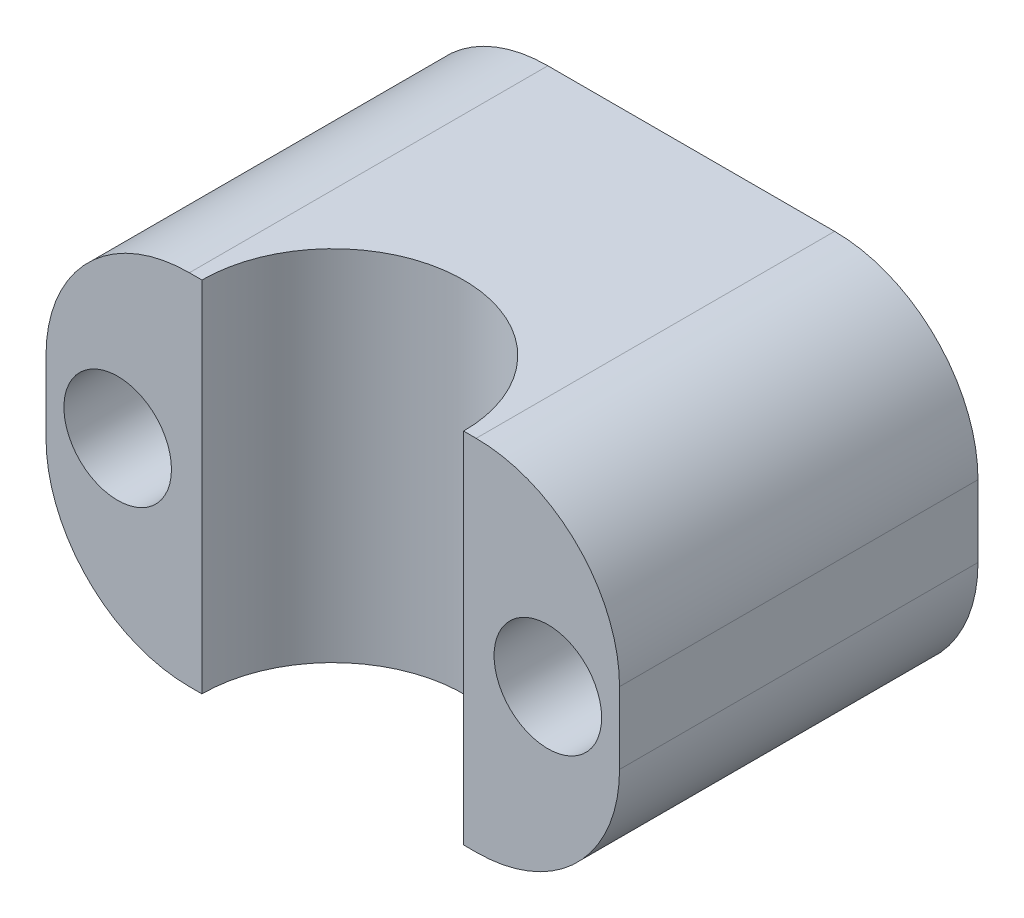
SolidWorks part; units mm, degrees
ref_plane "Front" through (0, 0, 0) normal (0, 0, 1) x (1, 0, 0)
ref_plane "Top" through (0, 0, 0) normal (0, 1, 0) x (1, 0, 0)
ref_plane "Right" through (0, 0, 0) normal (1, 0, 0) x (0, 0, -1)
sketch "Эскиз1" plane through (0, 0, 0) normal (0, 0, 1) x (1, 0, 0)
  line L1 (-4, 5) -> (4, 5)
  line L2 (-8, 1) -> (-8, -1)
  line L3 (-4, -5) -> (4, -5)
  line L4 (8, 1) -> (8, -1)
  line L5 (-8, 5) -> (8, -5) construction
  line L6 (-8, -5) -> (8, 5) construction
  arc A0 (4, -5) -> (8, -1) centre (4, -1) ccw
  arc A1 (4, 5) -> (8, 1) centre (4, 1) cw
  arc A2 (-8, -1) -> (-4, -5) centre (-4, -1) ccw
  arc A3 (-4, 5) -> (-8, 1) centre (-4, 1) ccw
  point P0 (0, 0)
  dimension "D3" = 4
  dimension "D1" = 16
  dimension "D2" = 10
extrude "Бобышка-Вытянуть1" add sketch "Эскиз1" along normal blind 10
sketch "Эскиз2" plane through (0, 5, 0) normal (0, 1, 0) x (1, 0, 0)
  line L0 (4, -10) -> (-4, -10) construction
  circle A0 centre (0, -10) radius 3.65
  dimension "D1" = 7.3
extrude "Вырез-Вытянуть1" cut sketch "Эскиз2" against normal up to next
sketch "Эскиз3" plane through (0, 0, 10) normal (0, 0, 1) x (1, 0, 0)
  line L0 (0, 5) -> (0, -5) construction
  line L1 (3.65, 5) -> (-3.65, 5) construction
  line L2 (-3.65, -5) -> (3.65, -5) construction
  line L3 (-6, 0) -> (6, 0) construction
  circle A0 centre (-6, 0) radius 1.5
  circle A1 centre (6, 0) radius 1.5
  point P10 (0, 0)
  dimension "D1" = 12
extrude "Вырез-Вытянуть2" cut sketch "Эскиз3" against normal up to next
